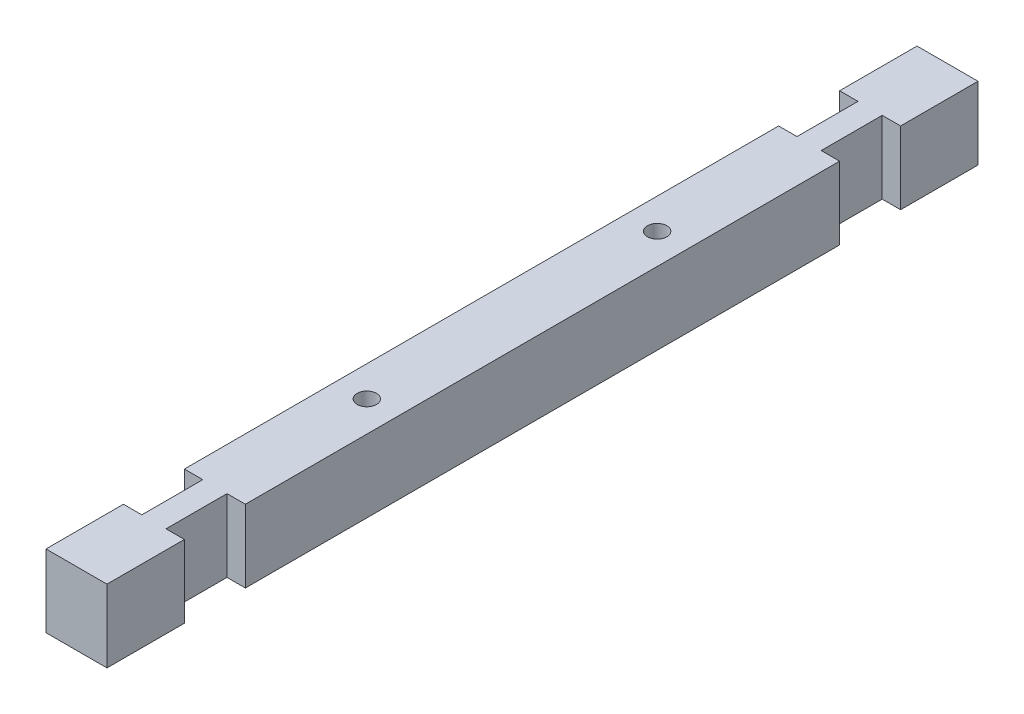
SolidWorks part; units mm, degrees
ref_plane "Front" through (0, 0, 0) normal (0, 0, 1) x (1, 0, 0)
ref_plane "Top" through (0, 0, 0) normal (0, 1, 0) x (1, 0, 0)
ref_plane "Right" through (0, 0, 0) normal (1, 0, 0) x (0, 0, -1)
sketch "Esquisse1" plane through (0, 0, 0) normal (0, 0, 1) x (1, 0, 0)
  line L1 (0, 0) -> (63, 0)
  line L2 (0, 0) -> (0, 75)
  line L3 (0, 75) -> (63, 75)
  line L4 (63, 0) -> (63, 75)
  dimension "D1" = 63
  dimension "D2" = 75
extrude "Boss.-Extru.1" add sketch "Esquisse1" along normal blind 900
sketch "Esquisse2" plane through (63, 0, 0) normal (1, 0, 0) x (0, 0, -1)
  line L0 (-450, 75) -> (-450, 0) construction
  line L1 (-900, 75) -> (0, 75) construction
  line L2 (-900, 0) -> (0, 0) construction
  line L3 (-900, 0) -> (-900, 75) construction
  line L4 (-820, 75) -> (-757, 75)
  line L5 (-820, 75) -> (-820, 0)
  line L6 (-820, 0) -> (-757, 0)
  line L7 (-757, 75) -> (-757, 0)
  line L8 (-143, 75) -> (-143, 0)
  line L9 (-80, 0) -> (-143, 0)
  line L10 (-80, 75) -> (-80, 0)
  line L11 (-80, 75) -> (-143, 75)
  point P10 (-820, 37.5)
  dimension "D1" = 80
  dimension "D2" = 63
extrude "Enlèv. mat.-Extru.1" cut sketch "Esquisse2" against normal blind 19
extrude "Enlèv. mat.-Extru.2" cut sketch "Esquisse2<2>" along normal blind 19 from vertex starting at point (0, 75, 900)
sketch "Esquisse2<2>" plane through (63, 0, 0) normal (1, 0, 0) x (0, 0, -1) same geometry as "Esquisse2"
sketch "Esquisse3" plane through (0, 75, 0) normal (0, 1, 0) x (1, 0, 0)
  line L0 (31.5, 0) -> (31.5, -900) construction
  line L1 (63, 0) -> (0, 0) construction
  line L2 (63, -900) -> (0, -900) construction
  line L3 (0, -450) -> (63, -450) construction
  line L4 (0, -757) -> (0, -143) construction
  line L5 (63, -757) -> (63, -143) construction
  circle A0 centre (31.5, -300) radius 10
  circle A1 centre (31.5, -600) radius 10
  dimension "D1" = 20
  dimension "D2" = 300
extrude "Enlèv. mat.-Extru.3" cut sketch "Esquisse3" against normal through all
